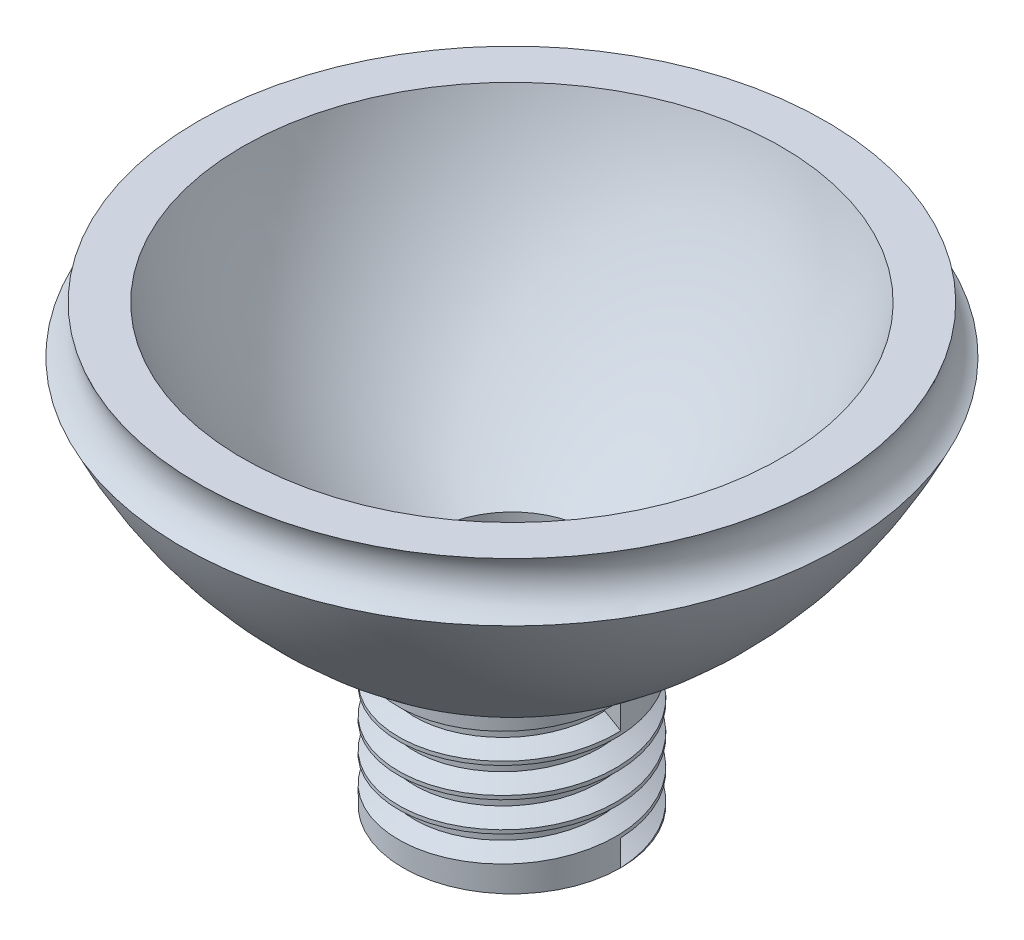
SolidWorks part; units mm, degrees
ref_plane "Front Plane" through (0, 0, 0) normal (0, 0, 1) x (1, 0, 0)
ref_plane "Top Plane" through (0, 0, 0) normal (0, 1, 0) x (1, 0, 0)
ref_plane "Right Plane" through (0, 0, 0) normal (1, 0, 0) x (0, 0, -1)
sketch "Sketch1" plane through (0, 0, 0) normal (0, 0, 1) x (1, 0, 0)
  line L0 (0, 41.5022) -> (0, -32.4593) construction
  line L5 (13.625, 0) -> (17.625, 0)
  line L6 (4, -12) -> (4, -22)
  line L7 (4, -22) -> (5.5, -22)
  line L8 (5.5, -22) -> (5.5, -14)
  arc A0 (13.625, 0) -> (4, -12) centre (-5.5891, 5.5513) cw
  arc A1 (17.625, 0) -> (5.5, -14) centre (-5.991, 8.2026) cw
  dimension "D7" = 12
  dimension "D8" = 20
  dimension "D9" = 25
  dimension "D1" = 13.625
  dimension "D2" = 4
  dimension "D3" = 4
  dimension "D4" = 1.5
  dimension "D5" = 8
  dimension "D6" = 10
revolve "Revolve1" add sketch "Sketch1" angle 360 about L0
sketch "Sketch2" plane through (0, 0, 0) normal (1, 0, 0) x (0, 0, -1)
  line L0 (0, 2.8101) -> (0, -5.4094) construction
  line L1 (0, 0) -> (24.9984, 0) construction
  circle A0 centre (17.435, -0.8) radius 1.765
  dimension "D1" = 3.53
  dimension "D2" = 17.435
  dimension "D3" = 0.8
revolve "Cut-Revolve1" cut sketch "Sketch2" angle 360 about L0
thread "Thread1" pitch 1.5 method cut profile "Thread Profile1" start angle 0, offset 0, length 6, pitch 1.5, diameter 11
ref_plane "Plane1" through (5.5, -22, 0) normal (0, 0, 1) x (1, 0, 0)
sketch "Thread Profile1" plane through (5.5, -22, 0) normal (0, 0, 1) x (1, 0, 0)
  line L0 (0, 0) -> (0, 1.5) construction
  line L11 (0, 0) -> (0, 1.3125)
  line L12 (0, 1.3125) -> (-0.8119, 0.8437)
  line L13 (-0.8119, 0.8437) -> (-0.8119, 0.4687)
  line L15 (-0.8119, 0.4687) -> (0, 0)
  line L17 (-0.8119, 0.6562) -> (0, 0.6562) construction
  point P2 (0, 0)
  dimension "Pitch" = 1.5
  dimension "Profile_Angle" = 60
  dimension "Profile_Land" = 0.375
  dimension "Profile_Height" = 0.8119
